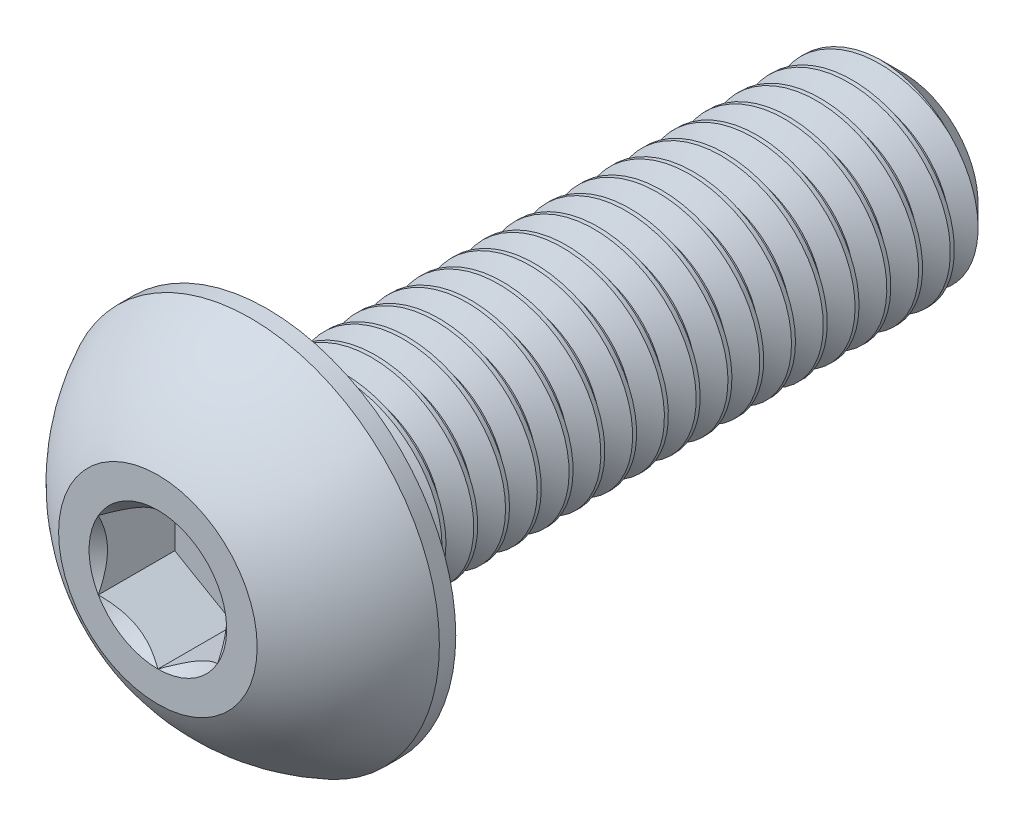
SolidWorks part; units mm, degrees
note: '?' marks a value the reader was unsure of.
ref_plane "Front" through (0, 0, 0) normal (0, 0, 1) x (1, 0, 0)
ref_plane "Top" through (0, 0, 0) normal (0, 1, 0) x (1, 0, 0)
ref_plane "Right" through (0, 0, 0) normal (1, 0, 0) x (0, 0, -1)
sketch "Sketch1" plane through (0, 0, 0) normal (1, 0, 0) x (0, 0, -1)
  line L2 (2.75, 2.5) -> (18.75, 2.5)
  line L3 (18.75, 2.5) -> (18.75, 0)
  line L4 (18.75, 0) -> (2.75, 0)
  line L6 (2.3375, 4.75) -> (2.75, 4.75) construction
  line L7 (18.75, 2.5) -> (18.75, -2.5) construction
  line L8 (0, 0) -> (2.75, 0) construction
  line L9 (2.75, 4.75) -> (2.75, -4.75) construction
  line L11 (2.75, 2.5) -> (2.75, 0)
  line L13 (0, 1.5) -> (0, -1.5) construction
  line L14 (0, 1.5) -> (0, 2.5) construction
  arc A3 (0, 2.5) -> (2.3375, 4.75) centre (4.6581, 0) cw construction
  dimension "D1" = 0.4125
revolve "Revolve1" add sketch "Sketch1" angle 360 mid plane about L4
sketch "Sketch3" plane through (0, 0, -18.75) normal (0, 0, -1) x (-1, 0, 0)
  circle A0 centre (0, 0) radius 2.5
curve "Helix/Spiral1" pitch 0.8 height 16.8 turns 21
chamfer "Chamfer1" distance 0.6 angle 45 1 edges at (-2.5, 0, -18.75)
sketch "Sketch7" plane through (0, 0, 0) normal (1, 0, 0) x (0, 0, -1)
  line L6 (2.3375, 4.75) -> (2.75, 4.75) construction
  line L8 (0, 0) -> (2.75, 0) construction
  line L11 (2.75, 4.75) -> (2.75, -4.75) construction
  line L12 (2.3375, 4.75) -> (2.75, 4.75)
  line L13 (0, 0) -> (2.75, 0)
  line L14 (0, 1.5) -> (0, -1.5) construction
  line L15 (2.75, 4.75) -> (2.75, 0)
  line L16 (0, 2.5) -> (0, 0)
  arc A2 (2.3375, 4.75) -> (0, 2.5) centre (4.6581, 0) ccw construction
  arc A3 (2.3375, 4.75) -> (0, 2.5) centre (4.6581, 0) ccw
revolve "Revolve2" add sketch "Sketch7" angle 360 mid plane about L13
sketch "Sketch5" plane through (0, 0, 0) normal (0, 0, 1) x (1, 0, 0)
  line L1 (1.5, -0.866) -> (1.5, 0.866)
  line L2 (1.5, 0.866) -> (0, 1.7321)
  line L3 (0, 1.7321) -> (-1.5, 0.866)
  line L4 (-1.5, 0.866) -> (-1.5, -0.866)
  line L5 (-1.5, -0.866) -> (0, -1.7321)
  line L6 (0, -1.7321) -> (1.5, -0.866)
  circle A0 centre (0, 0) radius 1.5 construction
extrude "Cut-Extrude2" cut sketch "Sketch5" against normal blind 1.925
sketch "Sketch6" plane through (0, 0, 0) normal (0, 0, 1) x (1, 0, 0)
  circle A0 centre (0, 0) radius 1.7321
extrude "Cut-Extrude3" cut sketch "Sketch6" against normal blind 1.925 draft 45
sketch "Sketch2" plane through (0, 0, 0) normal (1, 0, 0) x (0, 0, -1)
  line L0 (18.15, 2.5) -> (18.85, 2.5)
  line L1 (18.85, 2.5) -> (18.55, 1.9804)
  line L2 (18.55, 1.9804) -> (18.45, 1.9804)
  line L3 (18.45, 1.9804) -> (18.15, 2.5)
  line L4 (18.3, 2.2402) -> (18.7, 2.2402) construction
  dimension "D1" = 60
  dimension "D2" = 0.1
  dimension "D3" = 0.4
sweep "Cut-Sweep1" cut profiles "Sketch2" path "Helix/Spiral1"
sketch "Sketch10" plane through (0, 0, 0) normal (1, 0, 0) x (0, 0, -1)
  line L0 (18.75, 2.5) -> (18.75, -2.5) construction
  point P0 (17.55, -2.5)
  dimension "D1" = 1.2
ref_axis "Center Axis 1" through (0, 0, -8.1113) along (0, 0, 1)?
ref_plane "Contact Plane 1" through (0, 0, -2.75) normal (0, 0, -1) x (-1, 0, 0)
ref_plane "Contact Plane 2" through (0, 0, 0) normal (0, 0, 1) x (1, 0, 0)
equation "\"D3@Helix/Spiral1\" = \"Lg@Sketch1\" + \"D4@Helix/Spiral1\""
equation "\"D2@Sketch2\" = \"D4@Helix/Spiral1\" * .125"
equation "\"D3@Sketch2\" = \"D4@Helix/Spiral1\" * .5"
equation "\"D1@Chamfer1\" = \"D4@Helix/Spiral1\" * .75"
equation "\"D1@Cut-Extrude2\" = \"Head Ht@Sketch1\" * .7"
equation "\"D1@Sketch1\" = \"Head Ht@Sketch1\" * .15"
equation "\"D1@Sketch10\" = \"D4@Helix/Spiral1\" * 1.5"
equation "\"D1@Cut-Extrude3\" = \"D1@Cut-Extrude2\""
